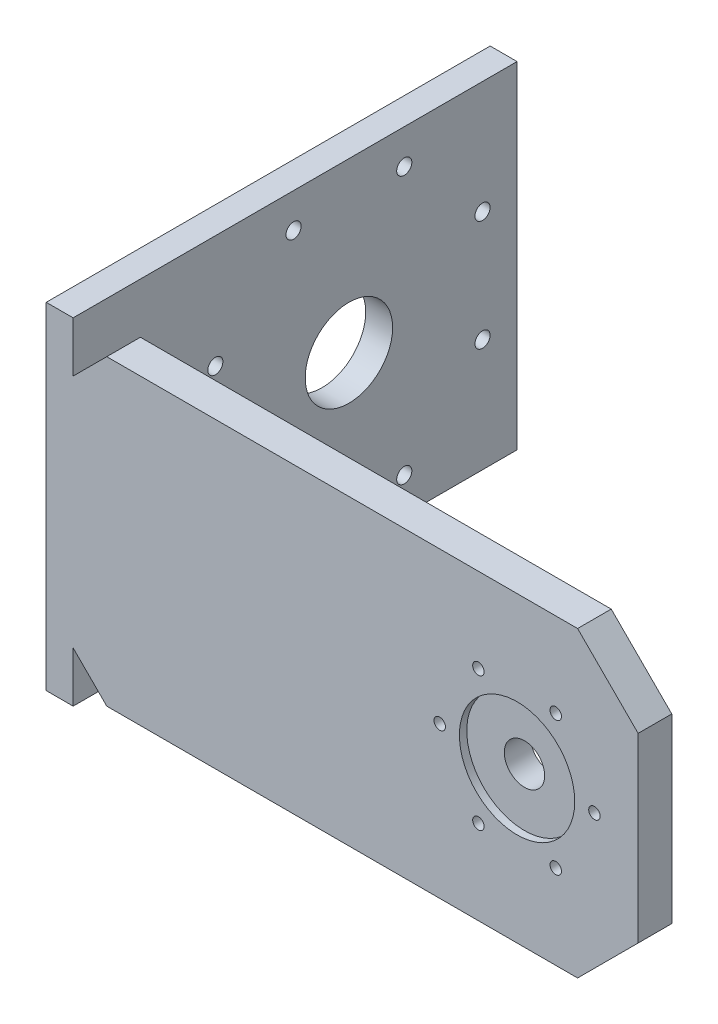
SolidWorks part; units mm, degrees
ref_plane "Front Plane" through (0, 0, 0) normal (0, 0, 1) x (1, 0, 0)
ref_plane "Top Plane" through (0, 0, 0) normal (0, 1, 0) x (1, 0, 0)
ref_plane "Right Plane" through (0, 0, 0) normal (1, 0, 0) x (0, 0, -1)
ref_plane "PL_Top_Plate_base" through (0, 0, 72) normal (0, 0, 1) x (1, 0, 0)
sketch "SK_Top_Plate" plane through (0, 0, 72) normal (0, 0, 1) x (1, 0, 0)
  line L0 (-122, -45) -> (18, -45)
  line L1 (18, -45) -> (36, -27)
  line L2 (36, -27) -> (36, 27)
  line L3 (36, 27) -> (18, 45)
  line L4 (18, 45) -> (-122, 45)
  line L5 (-122, 45) -> (-140, 27)
  line L6 (-140, 27) -> (-140, -27)
  line L7 (-140, -27) -> (-122, -45)
  circle A0 centre (23, 0) radius 1.7
  circle A1 centre (11.5, 19.9186) radius 1.7
  circle A2 centre (-11.5, 19.9186) radius 1.7
  circle A3 centre (-23, 0) radius 1.7
  circle A4 centre (-11.5, -19.9186) radius 1.7
  circle A5 centre (11.5, -19.9186) radius 1.7
  circle A6 centre (0, 0) radius 6
  dimension "D17_SK_Top_Plate" = 3.4
  dimension "D19_SK_Top_Plate" = 3.4
  dimension "D22_SK_Top_Plate" = 3.4
  dimension "D25_SK_Top_Plate" = 3.4
  dimension "D27_SK_Top_Plate" = 3.4
  dimension "D30_SK_Top_Plate" = 3.4
  dimension "D33_SK_Top_Plate" = 12
  dimension "P1" = 122
  dimension "P2" = 45
  dimension "P3" = 18
  dimension "P4" = 45
  dimension "P5" = 36
  dimension "P6" = 27
  dimension "P7" = 36
  dimension "P8" = 27
  dimension "P9" = 18
  dimension "P10" = 45
  dimension "P11" = 122
  dimension "P12" = 45
  dimension "P13" = 140
  dimension "P14" = 27
  dimension "P15" = 140
  dimension "P16" = 27
  dimension "P18" = 23
  dimension "P20" = 11.5
  dimension "P21" = 19.9186
  dimension "P23" = 11.5
  dimension "P24" = 19.9186
  dimension "P26" = 23
  dimension "P28" = 11.5
  dimension "P29" = 19.9186
  dimension "P31" = 11.5
  dimension "P32" = 19.9186
extrude "Top_Plate" add sketch "SK_Top_Plate" along normal blind 10
ref_plane "PL_Yaw_Pilot_Recess_base" through (0, 0, 82) normal (0, 0, 1) x (1, 0, 0)
sketch "SK_Yaw_Pilot_Recess" plane through (0, 0, 82) normal (0, 0, 1) x (1, 0, 0)
  circle A0 centre (0, 0) radius 17.15
  dimension "D1_SK_Yaw_Pilot_Recess" = 34.3
extrude "Yaw_Pilot_Recess" cut sketch "SK_Yaw_Pilot_Recess" against normal blind 2.2
ref_plane "PL_Back_Plate_base" through (-140, 0, 0) normal (1, 0, 0) x (0, 0, -1)
sketch "SK_Back_Plate" plane through (-140, 0, 0) normal (1, 0, 0) x (0, 0, -1)
  line L0 (50, -50) -> (50, 50)
  line L1 (50, 50) -> (-82, 50)
  line L2 (-82, 50) -> (-82, -50)
  line L3 (-82, -50) -> (50, -50)
  circle A0 centre (39.7268, 16.4554) radius 2.25
  circle A1 centre (16.4554, 39.7268) radius 2.25
  circle A2 centre (-16.4554, 39.7268) radius 2.25
  circle A3 centre (-39.7268, 16.4554) radius 2.25
  circle A4 centre (-39.7268, -16.4554) radius 2.25
  circle A5 centre (-16.4554, -39.7268) radius 2.25
  circle A6 centre (16.4554, -39.7268) radius 2.25
  circle A7 centre (39.7268, -16.4554) radius 2.25
  circle A8 centre (0, 0) radius 13
  dimension "D9_SK_Back_Plate" = 4.5
  dimension "D12_SK_Back_Plate" = 4.5
  dimension "D15_SK_Back_Plate" = 4.5
  dimension "D18_SK_Back_Plate" = 4.5
  dimension "D21_SK_Back_Plate" = 4.5
  dimension "D24_SK_Back_Plate" = 4.5
  dimension "D27_SK_Back_Plate" = 4.5
  dimension "D30_SK_Back_Plate" = 4.5
  dimension "D33_SK_Back_Plate" = 26
  dimension "P1" = 50
  dimension "P2" = 50
  dimension "P3" = 50
  dimension "P4" = 50
  dimension "P5" = 82
  dimension "P6" = 50
  dimension "P7" = 82
  dimension "P8" = 50
  dimension "P10" = 39.7268
  dimension "P11" = 16.4554
  dimension "P13" = 16.4554
  dimension "P14" = 39.7268
  dimension "P16" = 16.4554
  dimension "P17" = 39.7268
  dimension "P19" = 39.7268
  dimension "P20" = 16.4554
  dimension "P22" = 39.7268
  dimension "P23" = 16.4554
  dimension "P25" = 16.4554
  dimension "P26" = 39.7268
  dimension "P28" = 16.4554
  dimension "P29" = 39.7268
  dimension "P31" = 39.7268
  dimension "P32" = 16.4554
extrude "Back_Plate" add sketch "SK_Back_Plate" along normal blind 8
ref_plane "PL_Rib_base" through (0, -4, 0) normal (0, 1, 0) x (1, 0, 0)
sketch "SK_Rib" plane through (0, -4, 0) normal (0, 1, 0) x (1, 0, 0)
  line L0 (-140, -52) -> (-30, -72)
  line L1 (-30, -72) -> (-140, -72)
  line L2 (-140, -72) -> (-140, -52)
  dimension "P1" = 140
  dimension "P2" = 52
  dimension "P3" = 30
  dimension "P4" = 72
  dimension "P5" = 140
  dimension "P6" = 72
extrude "Rib" add sketch "SK_Rib" along normal blind 8
equation "\"Yaw_face_z\" = 82"
equation "\"Roll_rear_x\" = -132"
